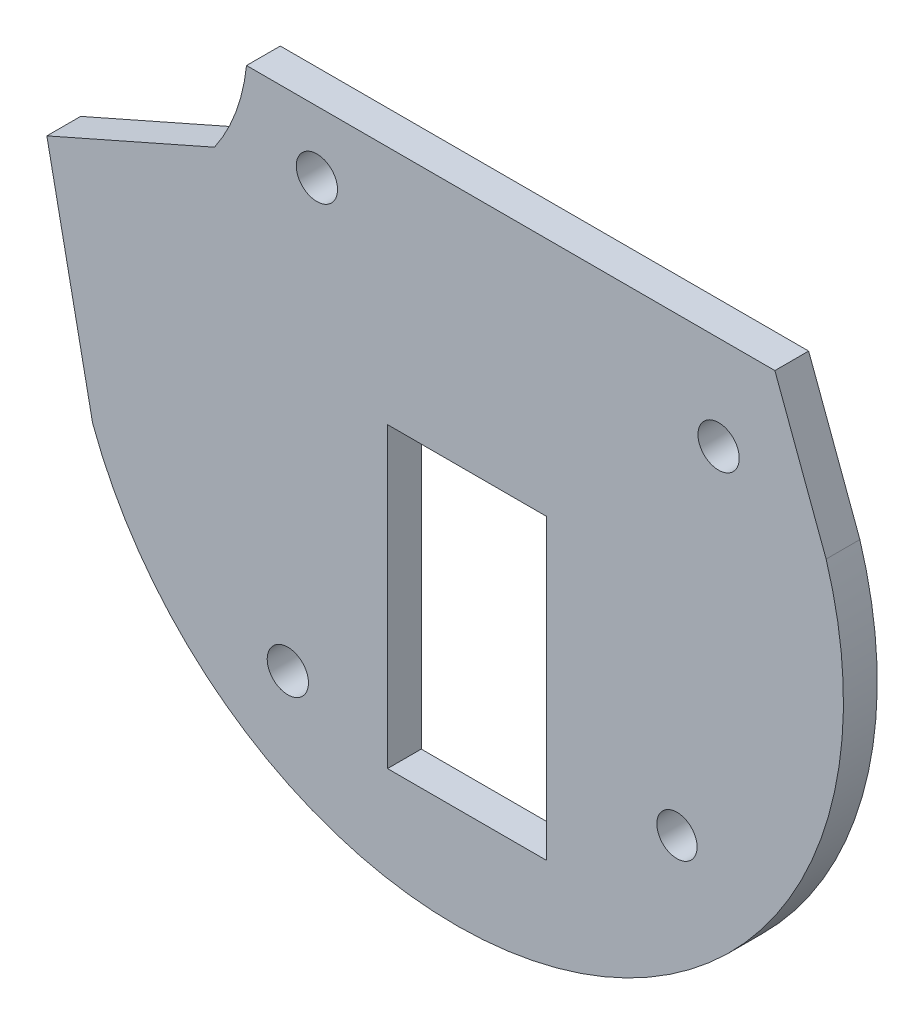
SolidWorks part; units mm, degrees
ref_plane "Front Plane" through (0, 0, 0) normal (0, 0, 1) x (1, 0, 0)
ref_plane "Top Plane" through (0, 0, 0) normal (0, 1, 0) x (1, 0, 0)
ref_plane "Right Plane" through (0, 0, 0) normal (1, 0, 0) x (0, 0, -1)
sketch "Sketch5" plane through (0, 0, 0) normal (0, 0, -1) x (-0.0184, 0.9998, 0)
  line L0 (33.8067, 26.1862) -> (34.4639, -9.5778)
  line L1 (28.6302, -11.8533) -> (23.8302, -23.2927)
  line L2 (23.8302, -23.2927) -> (8.4862, -20.4775)
  line L3 (33.8067, 26.1862) -> (24.4257, 29.4824)
  line L4 (30.1797, -4.8908) -> (34.3764, -4.8137) construction
  line L5 (34.3764, -4.8137) -> (34.4639, -9.5778) construction
  line L6 (34.4639, -9.5778) -> (34.3766, -9.5968) construction
  line L7 (27.5277, 22.2602) -> (33.8767, 22.3769) construction
  line L8 (27.5277, 22.2602) -> (27.4143, 28.4323) construction
  line L9 (3.3631, 18.996) -> (-4.6952, 18.8479) construction
  line L10 (3.3631, 18.996) -> (3.2246, 26.5341) construction
  line L11 (30.1797, -4.8908) -> (30.2892, -10.847) construction
  line L12 (0.3178, -7.4078) -> (0.4754, -15.9798) construction
  line L13 (0.3178, -7.4078) -> (-6.2927, -7.5293) construction
  arc A0 (34.4639, -9.5778) -> (28.6302, -11.8533) centre (36.0016, -22.1359) ccw
  arc A1 (24.4257, 29.4824) -> (8.4862, -20.4775) centre (17.1235, 4.2895) ccw
  circle A2 centre (27.5277, 22.2602) radius 1.397
  circle A3 centre (30.1797, -4.8908) radius 1.397
  circle A4 centre (3.3631, 18.996) radius 1.3622
  circle A5 centre (0.3178, -7.4078) radius 1.397
extrude "Extrude1" add sketch "Sketch5" along normal blind 2.286
sketch "Sketch9" plane through (0, 0, -2.286) normal (0, 0, -1) x (-1, 0, 0)
  line L0 (-25.5606, 34.2821) -> (-4.7199, 34.2821) construction
  line L1 (10.2095, 34.2821) -> (-25.5606, 34.2821) construction
  line L2 (-4.7199, 34.2821) -> (-4.7199, 11.9301) construction
  line L3 (-4.7199, 34.2821) -> (10.2095, 34.2821) construction
  line L4 (7.4124, 0.1817) -> (4.586, 2.9187) construction
sketch "Sketch10" plane through (0, 0, -2.286) normal (0, 0, -1) x (-1, 0, 0)
  line L0 (-4.7199, 11.9301) -> (-4.7199, 10.4061) construction
  line L1 (-4.7199, 10.4061) -> (-7.4821, 10.4061) construction
  line L2 (-7.4821, 10.4061) -> (-7.4821, 13.4541) construction
  line L3 (-7.4821, 13.4541) -> (-1.9576, 13.4541) construction
  line L4 (-1.9576, 13.4541) -> (-1.9576, 10.4061) construction
  line L5 (-1.9576, 10.4061) -> (-4.7199, 10.4061) construction
  line L6 (-4.7199, 10.4061) -> (-4.7199, -2.1669) construction
  line L7 (-4.7199, -2.1669) -> (-10.1047, -2.1669) construction
  line L8 (-4.7199, -2.1669) -> (0.6649, -2.1669) construction
  line L9 (-10.1047, -2.1669) -> (-10.1047, 18.0007) construction
  line L10 (-4.7199, 18.0007) -> (-4.7199, -2.1669) construction
  line L11 (0.6649, 7.9169) -> (0.6649, 18.0007) construction
  line L12 (-10.1047, -2.1669) -> (-10.1047, 18.0007)
  line L13 (-10.1047, 18.0007) -> (0.6649, 18.0007)
  line L14 (0.6649, 7.9169) -> (0.6649, -2.1669) construction
  line L15 (-10.1047, -2.1669) -> (0.6649, -2.1669)
  line L16 (0.6649, -2.1669) -> (0.6649, 18.0007)
  line L17 (-4.7199, 7.9169) -> (20.5583, 7.9169) construction
  arc A0 (-29.0285, 24.9633) -> (20.63, 8.1085) centre (-3.9741, 17.1994) ccw construction
  point P19 (-4.7199, 7.9169)
extrude "Extrude2" cut sketch "Sketch10" against normal up to surface (2.286 mm away) up to face at (17.5688, 3.7116, 0)
